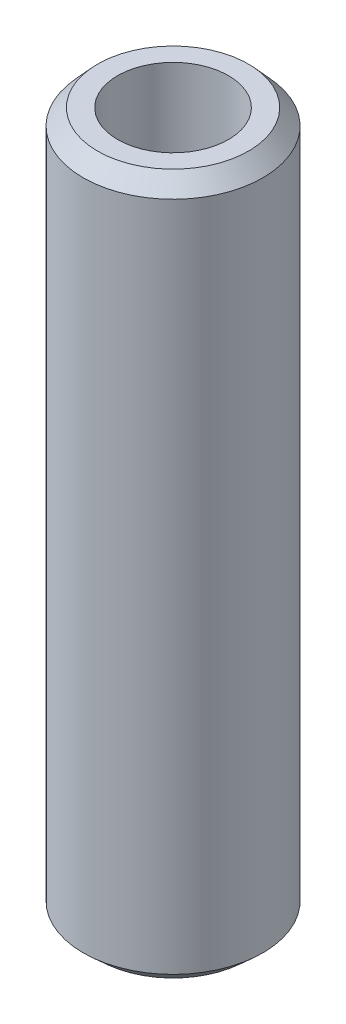
SolidWorks part; units mm, degrees
ref_plane "Front Plane" through (0, 0, 0) normal (0, 0, 1) x (1, 0, 0)
ref_plane "Top Plane" through (0, 0, 0) normal (0, 1, 0) x (1, 0, 0)
ref_plane "Right Plane" through (0, 0, 0) normal (1, 0, 0) x (0, 0, -1)
sketch "Sketch1" plane through (0, 0, 0) normal (0, 1, 0) x (1, 0, 0)
  circle A0 centre (0, 0) radius 20
  dimension "SHAFT_OD" = 40
extrude "Boss-Extrude1" add sketch "Sketch1" along normal blind 156.1805
sketch "Sketch2" plane through (0, 0, 0) normal (0, 1, 0) x (1, 0, 0)
  circle A0 centre (0, 0) radius 12.334
  dimension "BORE_D" = 24.668
extrude "Cut-Extrude1" cut sketch "Sketch2" along normal through all
chamfer "Chamfer1" distance 3.5364 angle 42.186 2 edges at (0, 156.1805, 20) (0, 0, 20) first distance on face at (0, 156.1805, 20) first distance on face at (0, 0, 12.334)
